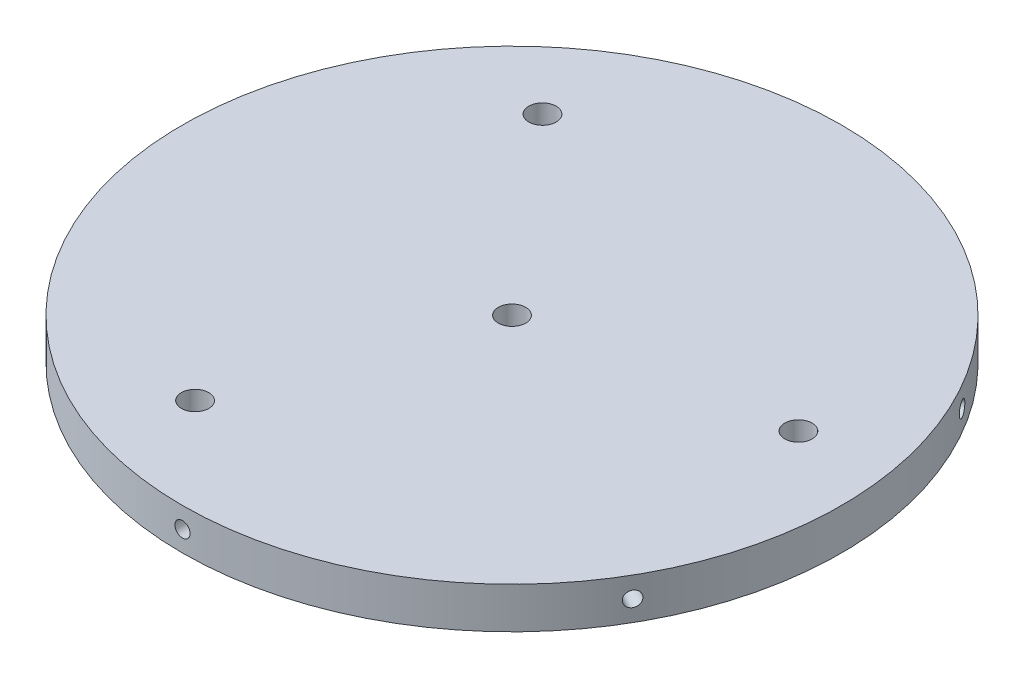
SolidWorks part; units mm, degrees
material "6061-T6 (SS)"
ref_plane "Front Plane" through (0, 0, 0) normal (0, 0, 1) x (1, 0, 0)
ref_plane "Top Plane" through (0, 0, 0) normal (0, 1, 0) x (1, 0, 0)
ref_plane "Right Plane" through (0, 0, 0) normal (1, 0, 0) x (0, 0, -1)
sketch "Sketch1" plane through (0, 0, 0) normal (0, 1, 0) x (1, 0, 0)
  line L0 (0, 0) -> (-50.3682, 60.0265)
  line L1 (0, 0) -> (50.3682, 60.0265)
  line L2 (0, 0) -> (0, 72.1431) construction
  circle A0 centre (0, 0) radius 78.359
  circle A1 centre (0, 0) radius 76.1746
  circle A2 centre (0, 0) radius 76.1746
  dimension "D1" = 156.718
  dimension "D2" = 152.3492
  dimension "D3" = 152.3492
  dimension "D4" = 80
extrude "Boss-Extrude1" add sketch "Sketch1" along normal blind 25.4 contours L2 A2 L1 A0 | L2 A1 L1 A2 | L2 A2 L1 A1 | L2 A0 L1 A2 | A2 L2 A1 L0 | A0 L2 A2 L0 | A2 L2 A0 L0 | A1 L2 A2 L0 region at (0, 0, 13.3592) region at (-23.5316, 0, -29.974) region at (-33.0764, 0, 70.9325) region at (-48.8794, 0, -59.85)
ref_plane "Plane1" through (0, 12.7, 0) normal (0, 1, 0) x (1, 0, 0)
sketch "Sketch6" plane through (0, 25.4, 0) normal (0, 1, 0) x (1, 0, 0)
  circle A0 centre (0, 0) radius 76.1746
  dimension "D1" = 152.3492
extrude "Boss-Extrude5" add sketch "Sketch6" along normal blind 9.525
sketch "Sketch7" plane through (0, 0, 0) normal (0, -1, 0) x (1, 0, 0)
  circle A0 centre (0, 0) radius 76.1746
  dimension "D1" = 152.3492
extrude "Boss-Extrude6" add sketch "Sketch7" along normal blind 9.525
sketch "Sketch8" plane through (0, -9.525, 0) normal (0, -1, 0) x (1, 0, 0)
  circle A0 centre (0, 0) radius 73.025
  dimension "D1" = 146.05
extrude "Cut-Extrude5" cut sketch "Sketch8" against normal up to surface (34.925 mm away) up to face at (0, 25.4, 76.1746)
ref_plane "Plane2" through (0, 0, -76.1746) normal (0, 0, -1) x (-1, 0, 0)
ref_plane "Plane5" through (0, 25.4, 0) normal (0, 1, 0) x (1, 0, 0)
ref_axis "Axis1" through (0, 0, 0) along (0, 1, 0)
sketch "Sketch3" plane through (0, 0, -76.1746) normal (0, 0, -1) x (-1, 0, 0)
  line L4 (76.1746, 0) -> (-76.1746, 0)
  line L5 (-76.1746, -9.525) -> (76.1746, -9.525)
  line L6 (76.1746, 25.4) -> (-76.1746, 25.4)
  line L7 (76.1746, 34.925) -> (-76.1746, 34.925)
  line L8 (0, 34.925) -> (0, 25.4) construction
  line L9 (0, 0) -> (0, -9.525) construction
  circle A0 centre (0, 30.1625) radius 1.75
  circle A1 centre (0, -4.7625) radius 1.75
  point P12 (0, 30.1625)
  point P13 (0, -4.7625)
  point P14 (-77.5445, 179.1871)
  dimension "D1" = 3.5
extrude "Cut-Extrude2" cut sketch "Sketch3" against normal blind 9.525 contours L8 A0 | L8 A0 | L9 A1 | L9 A1 region at (0, 30.1625, -76.1746) region at (0, -4.7625, -76.1746)
extrude "Cut-Extrude3" cut sketch "Sketch1<7>" against normal blind 9.525 from surface contours L2 A1 L1 A2 | A1 L2 A2 L0 | A2 L2 A0 L0 | L2 A2 L1 A0 region at (-23.5316, 0, -29.974) region at (-48.8794, 0, -59.85) starting at plane "Plane5"
sketch "Sketch1<7>" plane through (0, 0, 0) normal (0, 1, 0) x (1, 0, 0) same geometry as "Sketch1"
pattern_circular "CirPattern2" count 3 over 360 about axis through (0, 0, 0) along (0, 1, 0) of "Cut-Extrude3"
ref_plane "Plane3" through (0, 34.925, 0) normal (0, 1, 0) x (1, 0, 0)
sketch "Sketch4" plane through (0, 34.925, 0) normal (0, 1, 0) x (1, 0, 0)
  circle A0 centre (0, 0) radius 73.025
  dimension "D1" = 146.05
extrude "Boss-Extrude4" add sketch "Sketch4" against normal blind 9.525
pattern_circular "CirPattern3" count 6 over 360 about axis through (0, 0, 0) along (0, 1, 0) of "Cut-Extrude2"
sketch "Sketch9" plane through (0, 34.925, 0) normal (0, 1, 0) x (1, 0, 0)
  line L0 (0, 0) -> (-26.8004, -73.6334) construction
  circle A0 centre (0, 0) radius 3.175
  circle A1 centre (-19.5465, -53.7034) radius 3.175
  circle A2 centre (-36.7353, 43.7794) radius 3.175
  circle A3 centre (56.2818, 9.924) radius 3.175
  point P15 (0, 0)
  dimension "D1" = 6.35
  dimension "D2" = 6.35
  dimension "D3" = 57.15
  dimension "D5" = 3
extrude "Cut-Extrude6" cut sketch "Sketch9" against normal through all
sketch "Sketch10" plane through (0, 25.4, 0) normal (0, 1, 0) x (1, 0, 0)
  circle A0 centre (0, 0) radius 82.3228
extrude "Cut-Extrude7" cut sketch "Sketch10" against normal through all
equation "\"AB_Coupler_OD_Length\"= 1in"
equation "\"AB_Coupling_Section_Length\"= 0.375in"
equation "\"AB_Coupler_Length\"= \"AB_Coupler_OD_Length\" + \"AB_Coupling_Section_Length\" * 2"
equation "\"Cutout_Angle\" = 80"
equation "\"AB_Coupler_Num_Screws\"= 6"
equation "\"Num_Cutouts\" = 3"
equation "\"AB_Coupler_OD\"= 6.17in"
equation "\"AB_Coupler_ID\"= 5.75in"
equation "\"AB_Coupler_Surface_Diameter\"= 5.998in"
equation "\"D2@Sketch1\"=\"Bodytube_ID\""
equation "\"AB_Coupling_Screw_Diameter\"= 0.1065in"
equation "\"Aft_Section_Length\"= 40in"
equation "\"Aft_Lower_Length\"= 22in"
equation "\"Aft_Upper_Length\"= \"Aft_Section_Length\" - \"Aft_Lower_Length\" - \"AB_Coupler_OD_Length\""
equation "\"Mid_Coupler_Length\"= 13in"
equation "\"Lead_Screw_Dist\" = 2.25in"
equation "\"Lead_Screw_Diam\" = (27/64)*1in"
equation "\"Lead_Screw_Length\" = (\"Mid_Coupler_Length\" + 2*0.375in + 2*0.5in)"
equation "\"Bodytube_OD\" = 6.17in"
equation "\"Paddle_Pin_Offset\" = .25in"
equation "\"Bodytube_ID\" = 5.998in"
equation "\"Paddle_Pin_Radius\" = 2.25in"
equation "\"D1@Sketch4\"=\"AB_Coupler_ID\""
equation "\"D1@Sketch6\"=\"AB_Coupler_Surface_Diameter\""
equation "\"D1@Boss-Extrude5\"=\"AB_Coupling_Section_Length\""
equation "\"D1@Sketch7\"=\"AB_Coupler_Surface_Diameter\""
equation "\"D1@Boss-Extrude6\"=\"AB_Coupling_Section_Length\""
equation "\"D1@Sketch8\"=\"AB_Coupler_ID\""
equation "\"D3@Sketch9\"=\"Paddle_Pin_Radius\""
